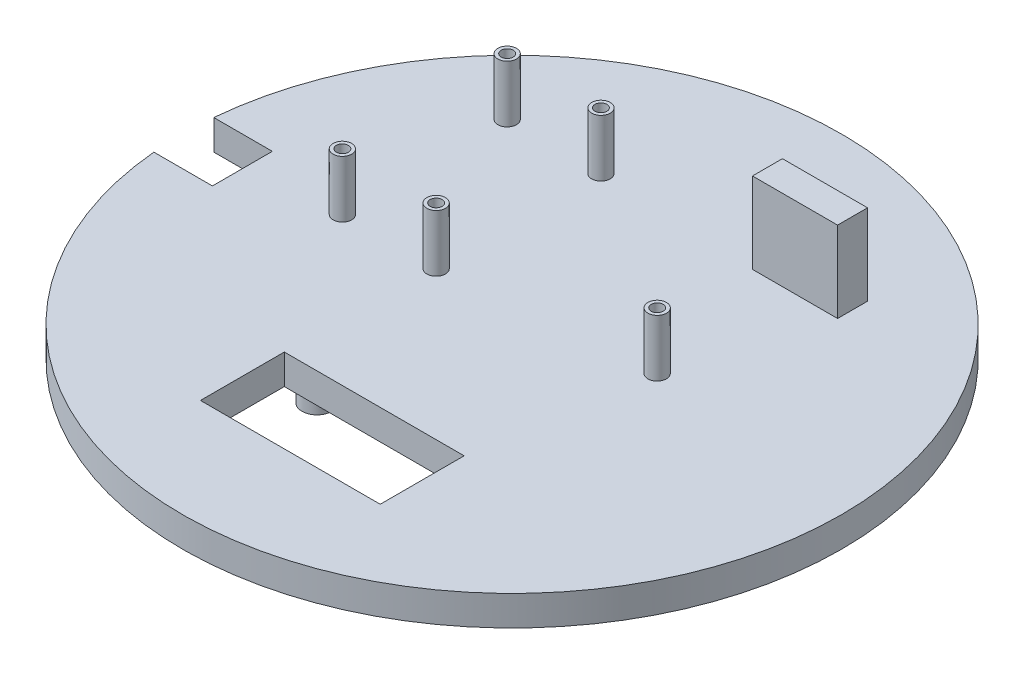
SolidWorks part; units mm, degrees
ref_plane "Front Plane" through (0, 0, 0) normal (0, 0, 1) x (1, 0, 0)
ref_plane "Top Plane" through (0, 0, 0) normal (0, 1, 0) x (1, 0, 0)
ref_plane "Right Plane" through (0, 0, 0) normal (1, 0, 0) x (0, 0, -1)
sketch "Sketch2" plane through (0, 0, 0) normal (0, 1, 0) x (1, 0, 0)
  line L0 (0, 0) -> (9.1621, 0) construction
  line L1 (0, 0) -> (0, 13.2968) construction
  line L3 (-15, -23) -> (15, -23)
  line L4 (-15, -23) -> (-15, -37)
  line L5 (-15, -37) -> (15, -37)
  line L6 (15, -23) -> (15, -37)
  line L7 (-15, -23) -> (15, -37) construction
  line L8 (-15, -37) -> (15, -23) construction
  circle A0 centre (0, 0) radius 55
  point P5 (0, -30)
  point P15 (-40, 0)
  dimension "D1" = 110
  dimension "D2" = 14
  dimension "D3" = 30
  dimension "D4" = 30
extrude "Boss-Extrude1" add sketch "Sketch2" along normal blind 5
sketch "Sketch3" plane through (0, 0, 0) normal (0, -1, 0) x (1, 0, 0)
  line L0 (0, 28.2554) -> (0, 35.9755) construction
  line L7 (-18.8316, 0) -> (-9.6455, 0) construction
  circle A0 centre (-21.95, 10.6) radius 2.5
  circle A1 centre (21.95, 10.6) radius 2.5
  circle A2 centre (21.95, -10.6) radius 2.5
  circle A3 centre (-21.95, -10.6) radius 2.5
  point P0 (0, 0)
  dimension "D3" = 5
  dimension "D1" = 10.6
  dimension "D2" = 21.95
  dimension "D4" = 10.6
extrude "Boss-Extrude2" add sketch "Sketch3" along normal blind 12
hole_wizard "Ø3.0mm Dowel Hole1" positions "3DSketch9" profile "Sketch13" hole size "Ø3.0" standard "DIN"
sketch3d "3DSketch9"
  line L0 (-21.95, -12, -10.6) -> (-21.95, 0, -10.6) construction
  line L1 (-21.95, -12, 10.6) -> (-21.95, 0, 10.6) construction
  line L2 (21.95, -12, -10.6) -> (21.95, 0, -10.6) construction
  line L3 (21.95, -12, 10.6) -> (21.95, 0, 10.6) construction
  point P0 (-21.95, -12, -10.6)
  point P4 (-21.95, -12, 10.6)
  point P8 (21.95, -12, -10.6)
  point P12 (21.95, -12, 10.6)
sketch "Sketch13" plane through (-21.95, -12, -10.6) normal (1, 0, 0) x (0, 0, -1)
  line L0 (0, 0) -> (0, 11.0513)
  line L1 (0, 11.0513) -> (1.5, 10.15)
  line L2 (1.5, 10.15) -> (1.5, 0)
  line L5 (1.5, 0) -> (0, 0)
  line L10 (0, 11.0513) -> (-1.5, 10.15) construction
  line L11 (0, -6.35) -> (0, 107.95) construction
  dimension "Hole Dia." = 3
  dimension "Hole Depth" = 10.15
  dimension "Drill Angle" = 118
sketch "Sketch15" plane through (0, 5, 0) normal (0, 1, 0) x (1, 0, 0)
  line L0 (-22.2011, 29.3371) -> (-22.2011, 35.4897) construction
  line L7 (-21.0891, 15.4599) -> (-18.0632, 15.4599) construction
  circle A0 centre (-30.0261, 29.2099) radius 1.55
  circle A1 centre (-14.3761, 29.2099) radius 1.55
  circle A2 centre (-14.3761, 1.7099) radius 1.55
  circle A3 centre (-30.0261, 1.7099) radius 1.55
  point P1 (0, 0)
  point P2 (0, 0)
  dimension "D3" = 3.1
  dimension "D6" = 7.825
  dimension "D5" = 15.4599
  dimension "D7" = 13.75
  dimension "D1" = 13.75
  dimension "D2" = 22.2011
  dimension "D4" = 7.825
extrude "Boss-Extrude3" add sketch "Sketch15" along normal blind 9.5
hole_wizard "Ø2.0mm Dowel Hole1" positions "3DSketch10" profile "Sketch16" hole size "Ø2.0" standard "DIN"
sketch3d "3DSketch10"
  line L0 (-30.0261, 14.5, -29.2099) -> (-30.0261, 5, -29.2099) construction
  line L1 (-30.0261, 14.5, -1.7099) -> (-30.0261, 5, -1.7099) construction
  line L2 (-14.3761, 14.5, -1.7099) -> (-14.3761, 5, -1.7099) construction
  line L3 (-14.3761, 14.5, -29.2099) -> (-14.3761, 5, -29.2099) construction
  point P0 (-30.0261, 14.5, -29.2099)
  point P4 (-30.0261, 14.5, -1.7099)
  point P8 (-14.3761, 14.5, -1.7099)
  point P12 (-14.3761, 14.5, -29.2099)
sketch "Sketch16" plane through (-30.0261, 14.5, -29.2099) normal (1, 0, 0) x (0, 0, 1)
  line L0 (0, 0) -> (0, 10.7509)
  line L1 (0, 10.7509) -> (1, 10.15)
  line L2 (1, 10.15) -> (1, 0)
  line L5 (1, 0) -> (0, 0)
  line L10 (0, 10.7509) -> (-1, 10.15) construction
  line L11 (0, -6.35) -> (0, 107.95) construction
  dimension "Hole Dia." = 2
  dimension "Hole Depth" = 10.15
  dimension "Drill Angle" = 118
sketch "Sketch17" plane through (0, 5, 0) normal (0, 1, 0) x (1, 0, 0)
  line L1 (12.1174, 33) -> (26.3174, 33)
  line L2 (12.1174, 33) -> (12.1174, 28)
  line L3 (12.1174, 28) -> (26.3174, 28)
  line L4 (26.3174, 33) -> (26.3174, 28)
  line L5 (12.1174, 33) -> (26.3174, 28) construction
  line L6 (12.1174, 28) -> (26.3174, 33) construction
  circle A0 centre (19.2174, 5) radius 1.55
  point P2 (19.2174, 30.5)
  point P8 (0, 0)
  point P9 (0, 0)
  dimension "D1" = 3.1
  dimension "D2" = 5
  dimension "D3" = 19.2174
  dimension "D4" = 23
  dimension "D5" = 14.2
  dimension "D6" = 5
extrude "Boss-Extrude4" add sketch "Sketch17" along normal blind 9.5
hole_wizard "Ø2.0mm Dowel Hole2" positions "3DSketch11" profile "Sketch18" hole size "Ø2.0" standard "DIN"
sketch3d "3DSketch11"
  line L0 (19.2174, 14.5, -5) -> (19.2174, 5, -5) construction
  point P0 (19.2174, 14.5, -5)
sketch "Sketch18" plane through (19.2174, 14.5, -5) normal (1, 0, 0) x (0, 0, 1)
  line L0 (0, 0) -> (0, 10.7509)
  line L1 (0, 10.7509) -> (1, 10.15)
  line L2 (1, 10.15) -> (1, 0)
  line L5 (1, 0) -> (0, 0)
  line L10 (0, 10.7509) -> (-1, 10.15) construction
  line L11 (0, -6.35) -> (0, 107.95) construction
  dimension "Hole Dia." = 2
  dimension "Hole Depth" = 10.15
  dimension "Drill Angle" = 118
sketch "Sketch19" plane through (0, 14.5, 0) normal (0, 1, 0) x (1, 0, 0)
  line L0 (26.3174, 28) -> (26.3174, 33) construction
  line L1 (12.1174, 28) -> (26.3174, 28) construction
  line L2 (12.1174, 33) -> (12.1174, 28) construction
  line L3 (26.3174, 33) -> (12.1174, 33) construction
  line L4 (26.3174, 28) -> (26.3174, 33)
  line L5 (12.1174, 28) -> (26.3174, 28)
  line L6 (12.1174, 33) -> (12.1174, 28)
  line L7 (26.3174, 33) -> (12.1174, 33)
extrude "Boss-Extrude5" add sketch "Sketch19" along normal blind 4
sketch "Sketch21" plane through (0, 5, 0) normal (0, 1, 0) x (1, 0, 0)
  line L8 (0, 0) -> (25.1353, 0) construction
  line L13 (25.1353, 0) -> (0, 0) construction
  line L14 (0, 0) -> (0, 20.9244) construction
  line L15 (-45, 5) -> (-45, -5)
  line L16 (-45, 5) -> (-55, 5)
  line L17 (-45, -5) -> (-55, -5)
  line L18 (-55, 5) -> (-55, -5)
  circle A2 centre (0, 0) radius 55 construction
  point P10 (-45, 0)
  dimension "D1" = 10
  dimension "D2" = 10
  dimension "D3" = 0
extrude "Cut-Extrude1" cut sketch "Sketch21" against normal through all
